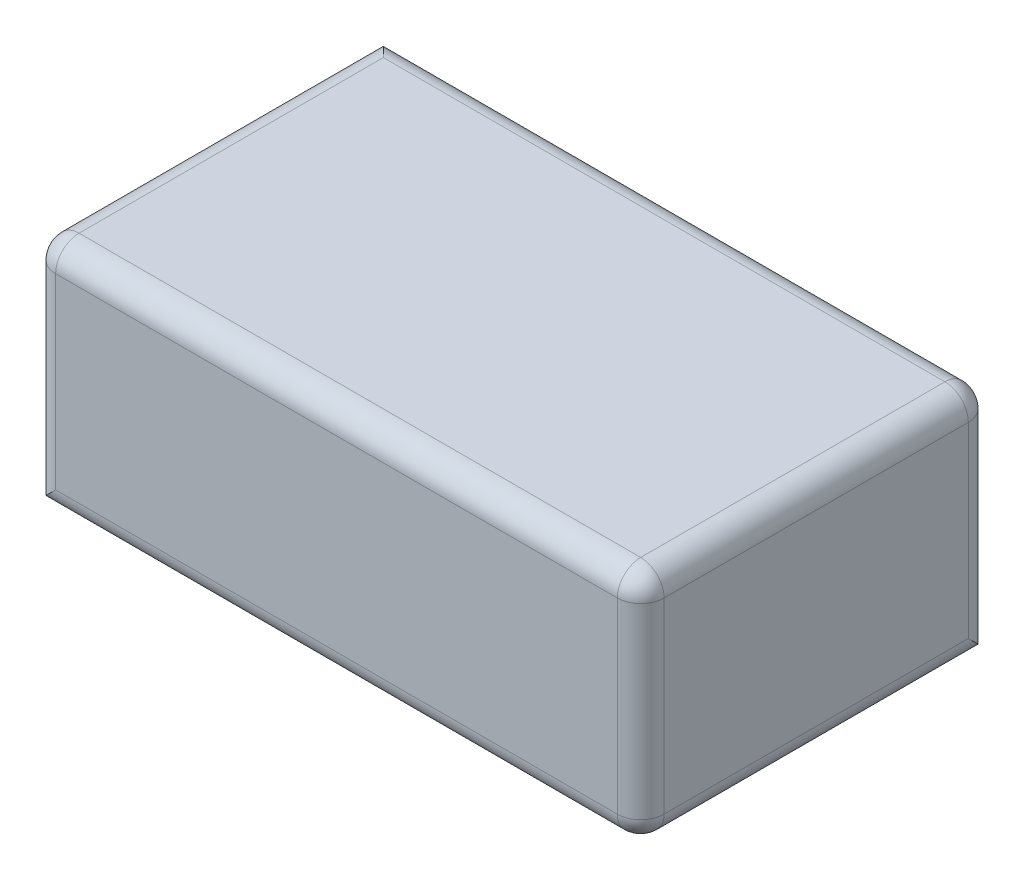
SolidWorks part; units mm, degrees
ref_plane "Front Plane" through (0, 0, 0) normal (0, 0, 1) x (1, 0, 0)
ref_plane "Top Plane" through (0, 0, 0) normal (0, 1, 0) x (1, 0, 0)
ref_plane "Right Plane" through (0, 0, 0) normal (1, 0, 0) x (0, 0, -1)
sketch "Sketch1" plane through (0, 0, 0) normal (0, 1, 0) x (1, 0, 0)
  line L1 (-26, -15) -> (26, -15)
  line L2 (-26, -15) -> (-26, 15)
  line L3 (-26, 15) -> (26, 15)
  line L4 (26, -15) -> (26, 15)
  line L5 (-26, -15) -> (26, 15) construction
  line L6 (-26, 15) -> (26, -15) construction
  point P0 (0, 0)
  dimension "D1" = 52
  dimension "D2" = 30
extrude "Boss-Extrude1" add sketch "Sketch1" along normal blind 20
fillet "Fillet1" radius 2 9 edges at (26, 0, 0) (0, 0, 15) (26, 20, 0) (0, 20, -15) (-26, 20, 0) (0, 20, 15) (26, 10, 15) (-26, 10, 15) (26, 10, -15)
